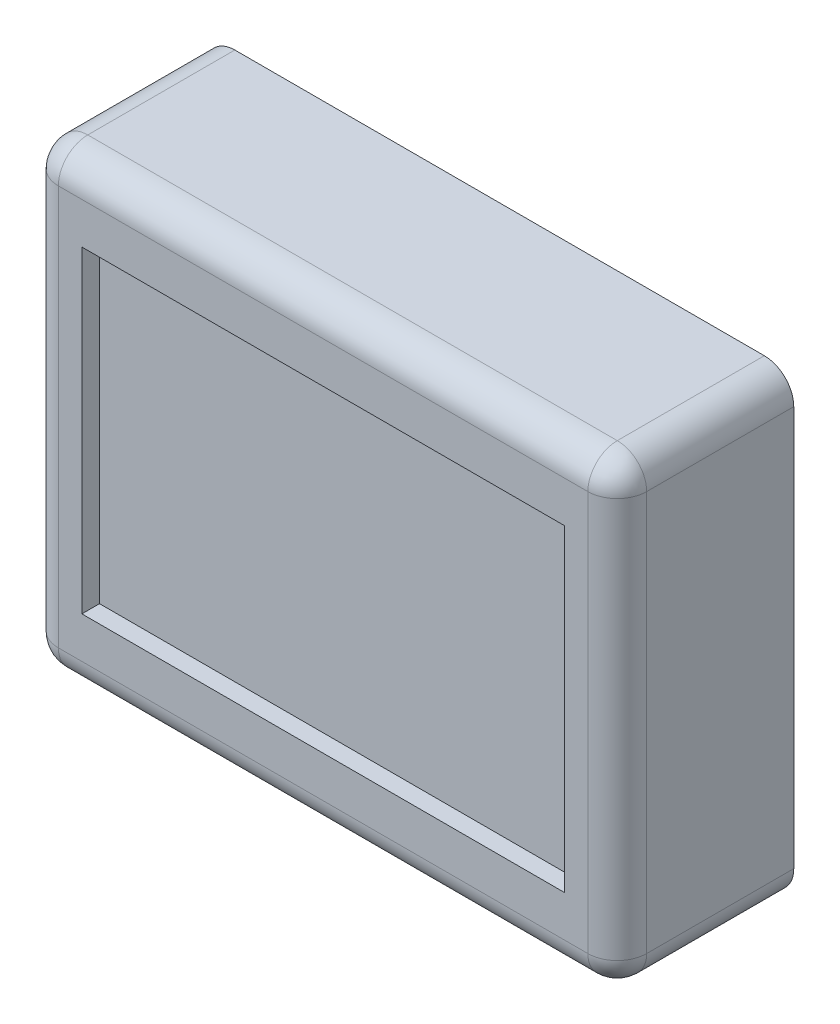
SolidWorks part; units mm, degrees
ref_plane "Front Plane" through (0, 0, 0) normal (0, 0, 1) x (1, 0, 0)
ref_plane "Top Plane" through (0, 0, 0) normal (0, 1, 0) x (1, 0, 0)
ref_plane "Right Plane" through (0, 0, 0) normal (1, 0, 0) x (0, 0, -1)
sketch "Sketch1" plane through (0, 0, 0) normal (0, 0, 1) x (1, 0, 0)
  line L0 (-41.8808, 54.2539) -> (-41.8808, -23.7461)
  line L1 (-41.8808, -23.7461) -> (58.1192, -23.7461)
  line L2 (58.1192, -23.7461) -> (58.1192, 54.2539)
  line L3 (58.1192, 54.2539) -> (-41.8808, 54.2539)
  line L4 (-32.8808, 42.2539) -> (-32.8808, -11.7461)
  line L5 (-32.8808, -11.7461) -> (49.1192, -11.7461)
  line L6 (49.1192, -11.7461) -> (49.1192, 42.2539)
  line L7 (49.1192, 42.2539) -> (-32.8808, 42.2539)
  dimension "D1" = 100
  dimension "D2" = 78
  dimension "D3" = 54
  dimension "D4" = 82
  dimension "D5" = 9
  dimension "D6" = 12
extrude "Boss-Extrude1" add sketch "Sketch1" against normal blind 30 contours L3 L0 L1 L2
sketch "Sketch3" plane through (0, 0, 0) normal (0, 0, 1) x (1, 0, 0)
  line L0 (-32.8808, 42.2539) -> (-32.8808, -11.7461)
  line L1 (-32.8808, -11.7461) -> (49.1192, -11.7461)
  line L2 (49.1192, -11.7461) -> (49.1192, 42.2539)
  line L3 (49.1192, 42.2539) -> (-32.8808, 42.2539)
  line L4 (-41.8808, 54.2539) -> (-41.8808, -23.7461) construction
  line L5 (-41.8808, -23.7461) -> (58.1192, -23.7461) construction
  dimension "D1" = 82
  dimension "D2" = 54
  dimension "D3" = 9
  dimension "D4" = 12
extrude "Cut-Extrude1" cut sketch "Sketch3" against normal blind 3 contours L3 L0 L1 L2
shell "Shell1" thickness 3 removed face at (8.1192, 15.2539, -30)
fillet "Fillet1" radius 5 8 edges at (58.1192, -23.7461, -15) (8.1192, -23.7461, 0) (-41.8808, -23.7461, -15) (-41.8808, 15.2539, 0) (-41.8808, 54.2539, -15) (58.1192, 54.2539, -15) (8.1192, 54.2539, 0) (58.1192, 15.2539, 0)
fillet "Fillet2" radius 5 2 edges at (55.1192, 15.2539, -3) (8.1192, 51.2539, -3)
